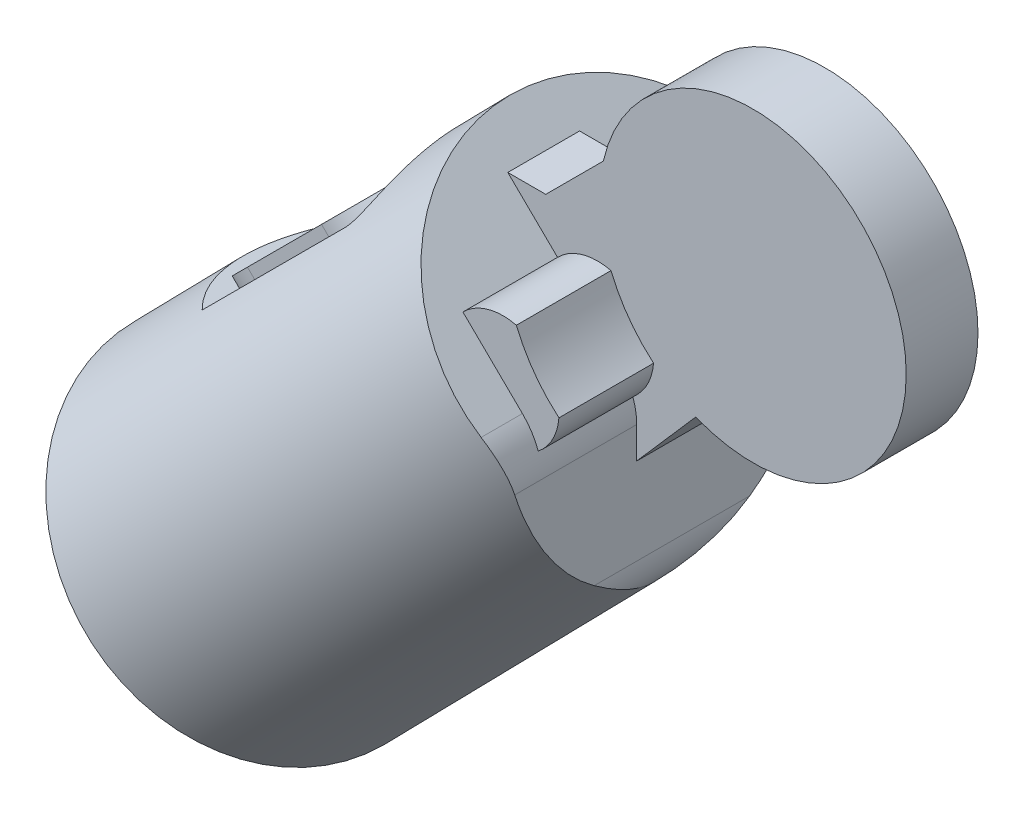
SolidWorks part; units mm, degrees
ref_plane "Front Plane" through (0, 0, 0) normal (0, 0, 1) x (1, 0, 0)
ref_plane "Top Plane" through (0, 0, 0) normal (0, 1, 0) x (1, 0, 0)
ref_plane "Right Plane" through (0, 0, 0) normal (1, 0, 0) x (0, 0, -1)
sketch "Sketch1" plane through (0, 0, 0) normal (1, 0, 0) x (0, 0, -1)
  line L0 (0, 304.8) -> (0, -304.8)
  dimension "D1" = 609.6
surface "Surface-Extrude1" [suppressed] sketch "Sketch1" parameters "D1"=609.6
sketch "Sketch2" plane through (0, 0, 0) normal (0, 0, 1) x (1, 0, 0)
  line L0 (-4.8859, 8.46) -> (97.4994, 113.1249) construction
  circle A0 centre (-4.8859, 8.46) radius 34.7138
extrude "Boss-Extrude1" add sketch "Sketch2" along normal mid plane 86.7319
sketch "Sketch3" plane through (0, 0, 0) normal (0, 0, 1) x (1, 0, 0)
  line L0 (22.6172, -2.9546) -> (39.9919, 15.7567)
  line L1 (41.7868, 15.8232) -> (42.8982, 14.7912)
  line L2 (42.8982, 14.7912) -> (48.0742, 14.7912)
  line L3 (48.982, 15.1731) -> (52.0648, 18.3245)
  line L4 (22.6172, -2.9546) -> (2.857, 16.3753)
  line L5 (-4.8859, 8.46) -> (97.4994, 113.1249) construction
  line L6 (2.857, 16.3753) -> (28.5152, 42.6048)
  line L7 (51.2923, 19.0802) -> (52.0648, 18.3245)
  line L8 (28.5152, 42.6048) -> (51.914, 19.7157)
  line L9 (51.914, 19.7157) -> (51.2923, 19.0802)
  arc A0 (39.9919, 15.7567) -> (41.7868, 15.8232) centre (40.9226, 14.8925) cw
  arc A1 (48.0742, 14.7912) -> (48.982, 15.1731) centre (48.0742, 16.0612) ccw
  dimension "D2" = 1.27
  dimension "D3" = 1.27
  dimension "D1" = 0.889
revolve "Revolve1" add sketch "Sketch3" angle 360 about L6
fillet "Fillet1" radius 2.54 1 edges at (29.8279, 8.46, 43.366)
sketch "Sketch4" plane through (0, 0, 0) normal (0, 0, 1) x (1, 0, 0)
  circle A0 centre (-4.8859, 8.46) radius 34.7138 construction
  circle A1 centre (-4.8859, 8.46) radius 34.7138
extrude "Cut-Extrude1" cut sketch "Sketch4" against normal mid plane 13.97
sketch "Sketch5" plane through (35.2409, 36.0255, 0) normal (0.6993, 0.7148, 0) x (0.7148, -0.6993, 0)
  circle A0 centre (-9.4086, 0) radius 33.8131 construction
  circle A1 centre (-9.4086, 0) radius 33.8131
extrude "Boss-Extrude2" add sketch "Sketch5" along normal blind 104.394
sketch "Sketch6" plane through (0, 0, 0) normal (0, 0, 1) x (1, 0, 0)
  line L0 (77.3445, 140.8755) -> (4.3439, 66.2496) construction
  line L1 (67.2924, 130.5996) -> (25.3327, 87.7057)
  line L2 (25.3327, 87.7057) -> (32.7632, 90.0029)
  line L3 (22.6165, 90.2277) -> (30.047, 92.5249) construction
  line L4 (32.7632, 90.0029) -> (61.4301, 118.6698)
  line L5 (70.8292, 128.0689) -> (52.031, 109.2707) construction
  line L10 (108.7928, 81.4255) -> (108.9187, 104.5772)
  line L11 (125.687, 93.5859) -> (77.3445, 140.8755) construction
  line L12 (105.0997, 113.7248) -> (125.687, 93.5859)
  line L13 (125.687, 93.5859) -> (105.1716, 72.6137)
  line L14 (52.6864, 18.96) -> (125.687, 93.5859) construction
  arc A1 (108.7928, 81.4255) -> (105.1716, 72.6137) centre (96.093, 81.4946) cw
  arc A2 (108.9187, 104.5772) -> (105.0997, 113.7248) centre (96.2189, 104.6462) ccw
  spline S0 degree 3 poles (61.4301, 118.6698) (64.5631, 121.8028) (65.3383, 126.623) (67.2924, 130.5996) knots 0 0 0 0 1 1 1 1
  dimension "D1" = 180
  dimension "D2" = 12.7
extrude "Cut-Extrude2" cut sketch "Sketch6" against normal through all and the other way through all
sketch "Sketch8" plane through (0, 0, 0) normal (0, 0, 1) x (1, 0, 0)
  line L0 (31.288, 88.5277) -> (29.8783, 89.9374)
  line L1 (29.8783, 89.9374) -> (60.2912, 120.3503)
  line L3 (60.2912, 120.3503) -> (63.299, 123.3581)
  line L4 (61.4301, 118.6698) -> (32.7632, 90.0029) construction
  line L5 (61.4301, 118.6698) -> (31.288, 88.5277)
  line L6 (61.4301, 118.6698) -> (64.7087, 121.9484)
  line L7 (64.7087, 121.9484) -> (63.299, 123.3581)
  dimension "D1" = 1.9936
extrude "Boss-Extrude3" add sketch "Sketch8" along normal mid plane 26.416 separate body
sketch "Sketch9" plane through (-30.0295, 30.0295, 0) normal (-0.7071, 0.7071, 0) x (0.7071, 0.7071, 0)
  circle A0 centre (111.3, 0) radius 9.0732
extrude "Boss-Extrude4" [suppressed] add sketch "Sketch9" along normal blind 1.905
sketch "Sketch10" [suppressed] plane through (-31.3766, 31.3766, 0) normal (-0.7071, 0.7071, 0) x (0.7071, 0.7071, 0)
  circle A2 centre (111.3, 0) radius 7.8032
  circle A3 centre (111.3, 0) radius 7.8032
  dimension "D1" = 1.27
extrude "Boss-Extrude5" [suppressed] add sketch "Sketch10" along normal blind 4.699
sketch "Sketch11" [suppressed] plane through (0, 0, 0) normal (0, 0, 1) x (1, 0, 0)
  line L0 (44.0017, 113.4003) -> (40.57, 116.832)
  line L1 (40.57, 116.832) -> (43.2009, 119.4629)
  line L2 (43.2009, 119.4629) -> (46.7224, 119.0131)
  line L3 (47.0018, 119.207) -> (47.0294, 119.3245)
  line L4 (47.4604, 119.4419) -> (48.7221, 118.1207)
  line L5 (48.7221, 118.1207) -> (44.0017, 113.4003)
  line L7 (49.5194, 118.918) -> (38.484, 107.8826) construction
  arc A0 (46.7224, 119.0131) -> (47.0018, 119.207) centre (46.7546, 119.265) ccw
  arc A1 (47.0294, 119.3245) -> (47.4604, 119.4419) centre (47.2767, 119.2665) cw
  point P5 (44.0017, 113.4003)
  dimension "D1" = 0.254
  dimension "D2" = 0.254
revolve "Revolve2" [suppressed] add sketch "Sketch11" angle 360 about L0
sketch "Sketch12" plane through (0, 0, 0) normal (0, 0, 1) x (1, 0, 0)
  line L0 (105.0997, 113.7248) -> (77.3445, 140.8755) construction
  line L1 (108.7928, 81.4255) -> (108.9187, 104.5772) construction
  line L2 (105.0997, 113.7248) -> (83.8353, 134.526)
  line L3 (108.8851, 98.3934) -> (108.9187, 104.5772)
  line L4 (83.8353, 134.526) -> (91.2221, 134.526)
  line L5 (91.2221, 134.526) -> (102.4333, 145.7373)
  line L6 (108.8851, 98.3934) -> (120.4118, 111.5902)
  arc A0 (108.9187, 104.5772) -> (105.0997, 113.7248) centre (96.2189, 104.6462) ccw construction
  arc A1 (108.9187, 104.5772) -> (105.0997, 113.7248) centre (96.2189, 104.6462) ccw
  circle A2 centre (131.547, 139.2593) radius 29.8257
  arc A3 (93.5169, 125.0554) -> (108.1757, 108.9269) centre (101.3203, 117.4219) cw
extrude "Boss-Extrude6" add sketch "Sketch12" along normal mid plane 50.8 contours A3 A2 L2 A1 region at (103.7429, 120.1579, 0)
extrude "Boss-Extrude7" add sketch "Sketch12<3>" along normal mid plane 13.97 contours A2 A3 | L2 A3 A2 L5 L4 | A2 A3 A1 L3 L6 | A3 A2 region at (95.9681, 133.4516, 0) region at (113.0934, 108.4273, 0) region at (108.6395, 122.7098, 0) region at (131.8227, 139.4584, 0)
sketch "Sketch12<3>" plane through (0, 0, 0) normal (0, 0, 1) x (1, 0, 0) same geometry as "Sketch12"
sketch "Sketch13" plane through (0, 0, 0) normal (0, 0, 1) x (1, 0, 0)
  line L0 (-11.0599, 81.3179) -> (67.0836, 4.8764)
  line L1 (-11.0599, 81.3179) -> (-83.2056, 7.5658)
  line L2 (67.0836, 4.8764) -> (-5.0621, -68.8757)
  line L3 (-83.2056, 7.5658) -> (-5.0621, -68.8757)
  line L4 (5.1164, 65.4939) -> (51.914, 19.7157) construction
extrude "Cut-Extrude3" cut sketch "Sketch13" against normal through all and the other way through all
sketch "Sketch14" [suppressed] plane through (-30.0295, 30.0295, 0) normal (-0.7071, 0.7071, 0) x (0.7071, 0.7071, 0)
  line L0 (100.505, 6.35) -> (122.095, -6.35) construction
  line L1 (100.505, 6.35) -> (122.095, 6.35)
  line L2 (100.505, 6.35) -> (100.505, -6.35) construction
  line L3 (100.505, -6.35) -> (122.095, -6.35)
  line L4 (122.095, 6.35) -> (122.095, -6.35) construction
  line L5 (100.505, 0) -> (98.5328, 7.3604) construction
  line L6 (100.505, 0) -> (98.5328, -7.3604) construction
  line L7 (111.3, 6.35) -> (111.3, -6.35) construction
  arc A0 (100.505, 7.62) -> (100.505, -7.62) centre (100.505, 0) ccw construction
  arc A1 (100.505, 6.35) -> (100.505, -6.35) centre (100.505, 0) ccw
  circle A2 centre (111.3, 0) radius 10.3432
  circle A3 centre (111.3, 0) radius 10.3432
  arc A4 (122.095, 6.35) -> (122.095, -6.35) centre (122.095, 0) cw
  circle A5 centre (111.3, 0) radius 3.7206 construction
  arc A6 (100.505, 7.112) -> (100.505, -7.112) centre (100.505, 0) ccw construction
  arc A7 (98.5328, 7.3604) -> (98.6643, 6.8697) centre (98.5986, 7.115) cw
  arc A8 (98.6643, 6.8697) -> (98.6643, -6.8697) centre (100.505, 0) ccw
  arc A9 (98.5328, 7.3604) -> (98.5328, -7.3604) centre (100.505, 0) ccw
  arc A10 (98.6643, -6.8697) -> (98.5328, -7.3604) centre (98.5986, -7.115) cw
  arc A11 (123.9357, -6.8697) -> (124.0672, -7.3604) centre (124.0015, -7.115) ccw
  arc A12 (124.0672, 7.3604) -> (124.0672, -7.3604) centre (122.095, 0) cw
  arc A13 (124.0672, 7.3604) -> (123.9357, 6.8697) centre (124.0015, 7.115) ccw
  arc A14 (123.9357, 6.8697) -> (123.9357, -6.8697) centre (122.095, 0) cw
  point P9 (111.3, 0)
  dimension "D2" = 15
  dimension "D3" = 15
  dimension "D6" = 12.7
  dimension "D7" = 21.59
  dimension "D1" = 1.27
  dimension "D4" = 0.762
  dimension "D5" = 1.27
extrude "Boss-Extrude8" [suppressed] add sketch "Sketch14" along normal blind 0.254 contours A4 L1 A3 L3 | A3 L1 A1 L3 | A13 A14 A11 A12 | A10 A8 A7 A9
sketch "Sketch15" plane through (-30.0295, 30.0295, 0) normal (-0.7071, 0.7071, 0) x (0, 0, 1)
  line L0 (-13.208, 131.9865) -> (-13.208, 84.7225) construction
  line L4 (13.208, 131.9865) -> (13.208, 84.7225) construction
  line L6 (-13.208, 131.9865) -> (-13.208, 118.5759)
  line L7 (-13.208, 84.7225) -> (-13.208, 98.1881)
  line L8 (13.208, 84.7225) -> (-13.208, 84.7225)
  line L9 (13.208, 84.7225) -> (13.208, 98.1881)
  line L10 (13.208, 131.9865) -> (13.208, 118.5759)
  line L11 (13.208, 131.9865) -> (-13.208, 131.9865)
  line L12 (-13.208, 118.5759) -> (-13.208, 127.3499)
  line L13 (-13.208, 98.1881) -> (-13.208, 84.7225)
  line L14 (13.208, 98.1881) -> (13.208, 84.7225)
  line L16 (13.208, 84.7225) -> (-13.208, 84.7225) construction
  arc A0 (-13.208, 118.5759) -> (13.208, 118.5759) centre (0, 118.5759) cw
  arc A1 (-13.208, 98.1881) -> (13.208, 98.1881) centre (0, 98.1881) ccw
  line M6 (-13.208, 131.9865) -> (-13.208, 84.7225)
  line M7 (-13.208, 84.7225) -> (13.208, 84.7225)
  line M8 (13.208, 84.7225) -> (13.208, 131.9865)
  line M9 (13.208, 131.9865) -> (-13.208, 131.9865)
extrude "Cut-Extrude6" cut sketch "Sketch15" against normal up to surface (1.9936 mm away) contours A1 M6 M7 M8 | L6 A0 M8 M9 M6 region at (63.2781, 123.3372, 0) region at (30.0395, 90.0986, 0) up to face at (47.0011, 104.2408, 0)
scale "Scale2" bodies to scale 123 120 102 scale about origin uniform scaling yes scale factor 2.102564
